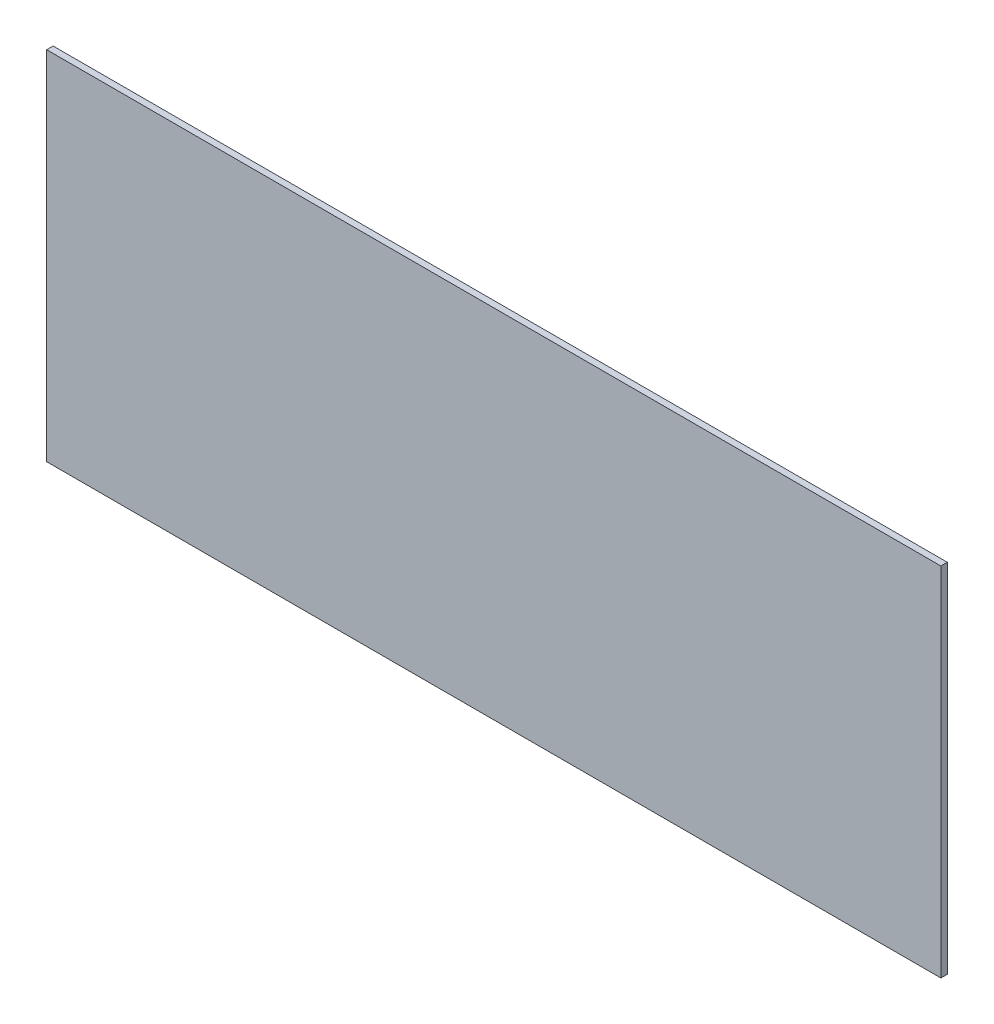
SolidWorks part; units mm, degrees
material "Beech"
ref_plane "Front Plane" through (0, 0, 0) normal (0, 0, 1) x (1, 0, 0)
ref_plane "Top Plane" through (0, 0, 0) normal (0, 1, 0) x (1, 0, 0)
ref_plane "Right Plane" through (0, 0, 0) normal (1, 0, 0) x (0, 0, -1)
sketch "Sketch1" plane through (0, 0, 0) normal (0, 0, 1) x (1, 0, 0)
  line L0 (158, 83) -> (-258, 83)
  line L1 (-258, 83) -> (-258, -83)
  line L2 (-258, -83) -> (158, -83)
  line L3 (158, -83) -> (158, 83)
  line L4 (155, 80) -> (-255, 80)
  line L5 (-255, 80) -> (-255, -80)
  line L6 (-255, -80) -> (155, -80)
  line L7 (155, -80) -> (155, 80)
  line L8 (155, 80) -> (-255, 80) construction
  line L9 (-255, 80) -> (-255, -80) construction
  line L10 (-255, -80) -> (155, -80) construction
  line L11 (155, -80) -> (155, 80) construction
  line L12 (158, 0) -> (-258, 0) construction
  line L13 (-50, -83) -> (-50, 83) construction
  dimension "D1" = 0
  dimension "D2" = 3
extrude "Boss-Extrude1" add sketch "Sketch1" along normal blind 3
